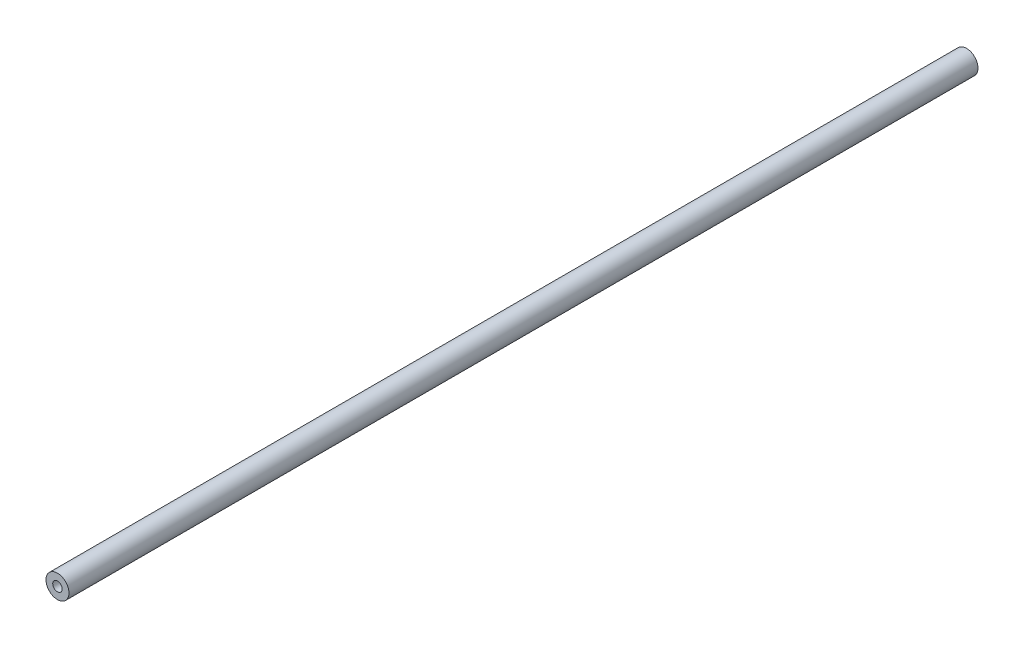
SolidWorks part; units mm, degrees
material "Латунь"
ref_plane "Спереди" through (0, 0, 0) normal (0, 0, 1) x (1, 0, 0)
ref_plane "Сверху" through (0, 0, 0) normal (0, 1, 0) x (1, 0, 0)
ref_plane "Справа" through (0, 0, 0) normal (1, 0, 0) x (0, 0, -1)
other "Configuration Table"
sketch "Эскиз1" plane through (0, 0, 0) normal (0, 0, 1) x (1, 0, 0)
  line L0 (235.7213, -388.4131) -> (236.321, -388.4131) construction
  circle A0 centre (0, 0) radius 4
  dimension "D1" = 8
extrude "Бобышка-Вытянуть1" add sketch "Эскиз1" along normal mid plane 316.4
sketch "Эскиз2" plane through (0, 0, 158.2) normal (0, 0, 1) x (1, 0, 0)
  circle A0 centre (0, 0) radius 1.25
  dimension "D1" = 2.5
sketch "Эскиз3" plane through (0, 0, -158.2) normal (0, 0, -1) x (-1, 0, 0)
  circle A0 centre (0, 0) radius 1.25
  dimension "D1" = 2.5
hole_wizard "Отверстие обработанное метчиком M4x0.72" positions "Эскиз4" profile "Эскиз5" tap size "M4x0.7" standard "Ansi Metric"
sketch "Эскиз4" plane through (0, 0, -158.2) normal (0, 0, -1) x (-1, 0, 0)
  point P0 (0, 0)
sketch "Эскиз5" plane through (0, 0, -158.2) normal (1, 0, 0) x (0, 1, 0)
  line L0 (0, 0) -> (0, 19.9914)
  line L1 (0, 19.9914) -> (1.65, 19)
  line L2 (1.65, 19) -> (1.65, 0)
  line L5 (1.65, 0) -> (0, 0)
  line L10 (0, 19.9914) -> (-1.65, 19) construction
  line L11 (0, -6.35) -> (0, 107.95) construction
  dimension "Диаметр сверла" = 3.3
  dimension "Глубина сверла" = 19
  dimension "Угол заточки сверла" = 118
hole_wizard "Отверстие обработанное метчиком M4x0.71" positions "Эскиз6" profile "Эскиз7" tap size "M4x0.7" standard "Ansi Metric"
sketch "Эскиз6" plane through (0, 0, 158.2) normal (0, 0, 1) x (1, 0, 0)
  point P0 (0, 0)
sketch "Эскиз7" plane through (0, 0, 158.2) normal (1, 0, 0) x (0, -1, 0)
  line L0 (0, 0) -> (0, 19.9914)
  line L1 (0, 19.9914) -> (1.65, 19)
  line L2 (1.65, 19) -> (1.65, 0)
  line L5 (1.65, 0) -> (0, 0)
  line L10 (0, 19.9914) -> (-1.65, 19) construction
  line L11 (0, -6.35) -> (0, 107.95) construction
  dimension "Диаметр сверла" = 3.3
  dimension "Глубина сверла" = 19
  dimension "Угол заточки сверла" = 118
sketch "Эскиз13" plane through (0, 0, 158.2) normal (0, 0, 1) x (1, 0, 0)
  line L0 (4, 0) -> (-4, 0) construction
  line L1 (0, 4) -> (0, -4) construction
  circle A0 centre (0, 0) radius 4 construction
